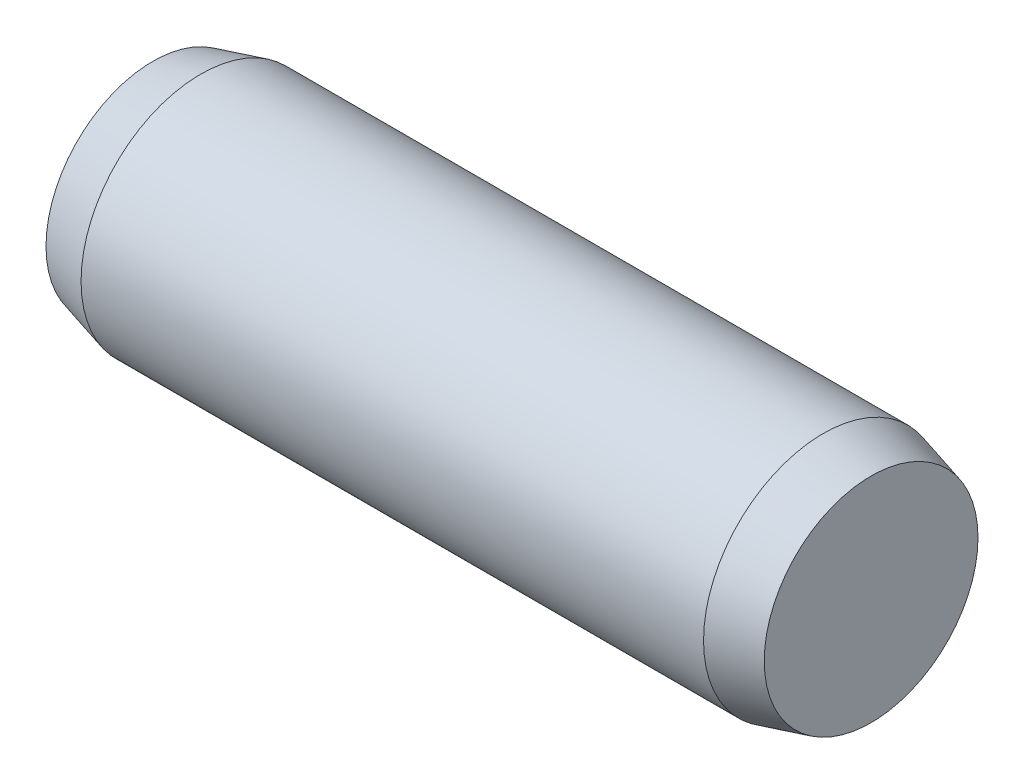
SolidWorks part; units mm, degrees
ref_plane "Front Plane" through (0, 0, 0) normal (0, 0, 1) x (1, 0, 0)
ref_plane "Top Plane" through (0, 0, 0) normal (0, 1, 0) x (1, 0, 0)
ref_plane "Right Plane" through (0, 0, 0) normal (1, 0, 0) x (0, 0, -1)
sketch "BodySke" plane through (0, 0, 0) normal (0, 1, 0) x (1, 0, 0)
  line L0 (0, 0) -> (33.9797, 0) construction
  line L1 (0, 5) -> (0, 0) construction
  line L2 (0, 5) -> (30, 5) construction
  line L3 (30, 5) -> (30, 0) construction
  line L4 (0, 0) -> (30, 0)
  line L5 (2, 5) -> (2, 0) construction
  line L6 (2, 5) -> (0, 4.4641)
  line L7 (15, 5) -> (15, 0) construction
  line L8 (28, 5) -> (30, 4.4641)
  line L9 (0, 4.4641) -> (0, 0)
  line L10 (30, 0) -> (30, 4.4641)
  line L11 (28, 5) -> (2, 5)
  dimension "Length" = 30
  dimension "Pin_dia" = 5
  dimension "Chamfer_length" = 2
  dimension "Ang" = 15
revolve "BaseBody" add sketch "BodySke" angle 360 about L0
